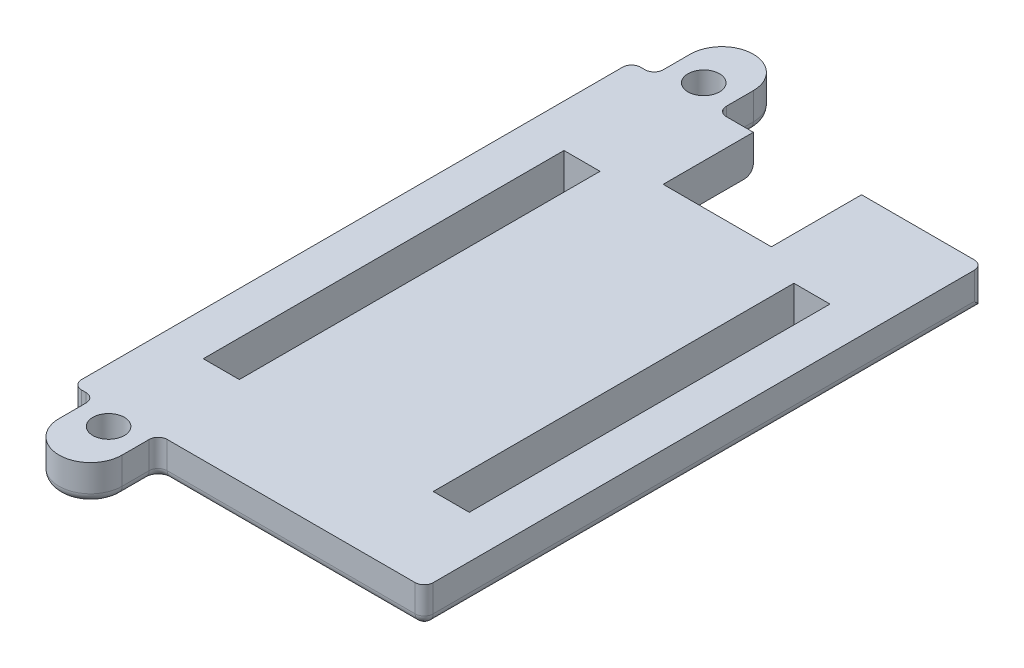
SolidWorks part; units mm, degrees
ref_plane "Front Plane" through (0, 0, 0) normal (0, 0, 1) x (1, 0, 0)
ref_plane "Top Plane" through (0, 0, 0) normal (0, 1, 0) x (1, 0, 0)
ref_plane "Right Plane" through (0, 0, 0) normal (1, 0, 0) x (0, 0, -1)
sketch "Sketch1" plane through (0, 0, 0) normal (0, 1, 0) x (1, 0, 0)
  line L0 (0, 31) -> (0, -31) construction
  line L1 (-19.5, 31) -> (19.5, 31)
  line L2 (-19.5, 31) -> (-19.5, -31)
  line L3 (-19.5, -31) -> (19.5, -31)
  line L4 (19.5, 31) -> (19.5, -31)
  line L5 (-19.5, 31) -> (19.5, -31) construction
  line L6 (-19.5, -31) -> (19.5, 31) construction
  line L7 (-14.75, 18.75) -> (-10.75, 18.75)
  line L8 (-14.75, 18.75) -> (-14.75, -21.25)
  line L9 (-14.75, -21.25) -> (-10.75, -21.25)
  line L10 (-10.75, 18.75) -> (-10.75, -21.25)
  line L11 (14.75, -21.25) -> (10.75, -21.25)
  line L12 (10.75, 18.75) -> (10.75, -21.25)
  line L13 (14.75, 18.75) -> (10.75, 18.75)
  line L14 (14.75, 18.75) -> (14.75, -21.25)
  line L15 (-19.5, 0) -> (19.5, 0) construction
  line L16 (0, -26) -> (0, 26) construction
  line L17 (-14.5, -26) -> (14.5, -26) construction
  line L18 (-14.5, -26) -> (-14.5, 26) construction
  line L19 (-14.5, 26) -> (14.5, 26) construction
  line L20 (14.5, -26) -> (14.5, 26) construction
  point P0 (0, 0)
  point P11 (-12.75, -21.25)
  point P26 (0, 0)
  dimension "D6" = 29
  dimension "D1" = 39
  dimension "D2" = 62
  dimension "D3" = 4
  dimension "D4" = 40
  dimension "D5" = 12.75
  dimension "D7" = 52
  dimension "D8" = 4.75
extrude "Base" add sketch "Sketch1" along normal blind 4
sketch "Sketch2" plane through (0, 0, 0) normal (0, 1, 0) x (1, 0, 0)
  line L0 (0, 0) -> (0, 31) construction
  line L1 (19.5, 31) -> (-19.5, 31) construction
  line L2 (-17, 31) -> (-10, 31)
  line L3 (-17, 31) -> (-17, 35)
  line L4 (-10, 31) -> (-10, 35)
  line L5 (-19.5, 0) -> (19.5, 0) construction
  line L6 (-19.5, 31) -> (-19.5, -31) construction
  line L7 (19.5, -31) -> (19.5, 31) construction
  line L8 (-17, -31) -> (-17, -35)
  line L9 (-17, -31) -> (-10, -31)
  line L10 (-10, -31) -> (-10, -35)
  circle A0 centre (-13.5, 33) radius 1.75
  arc A2 (-17, 35) -> (-10, 35) centre (-13.5, 35) cw
  arc A3 (-17, -35) -> (-10, -35) centre (-13.5, -35) ccw
  circle A4 centre (-13.5, -33) radius 1.75
  point P25 (0, 0)
  point P27 (-13.5, 31)
  dimension "D1" = 33
  dimension "D2" = 3.5
  dimension "D5" = 13.5
  dimension "D3" = 7
  dimension "D4" = 4
extrude "Mounting Ends" add sketch "Sketch2" along normal up to surface (4 mm away) up to face at (0, 4, 0)
sketch "Sketch3" plane through (0, 0, -31) normal (0, 0, -1) x (-1, 0, 0)
  line L0 (-19.5, 0) -> (10, 0) construction
  line L5 (-6, 0) -> (6, 0)
  line L6 (-6, 0) -> (-6, 4)
  line L7 (-6, 4) -> (6, 4)
  line L8 (6, 0) -> (6, 4)
  line L9 (-19.5, 4) -> (10, 4) construction
  dimension "D1" = 12
extrude "USB Opening" cut sketch "Sketch3" against normal blind 10
fillet "1mm Edge Fillets" radius 1 20 edges at (-18.25, 0, 31) (-17, 0, 33) (-10, 0, -33) (-13.5, 0, 38.5) (-13.5, 0, -38.5) (-10, 0, 33) (-17, 0, -33) (4.75, 0, 31) (19.5, 0, 0) (-18.25, 0, -31) (-19.5, 0, 0) (-19.5, 2, -31) (-17, 2, -31) (-10, 2, -31) (19.5, 2, -31) (-10, 2, 31) (-17, 2, 31) (19.5, 2, 31) (-19.5, 2, 31) (-8, 0, -31)
